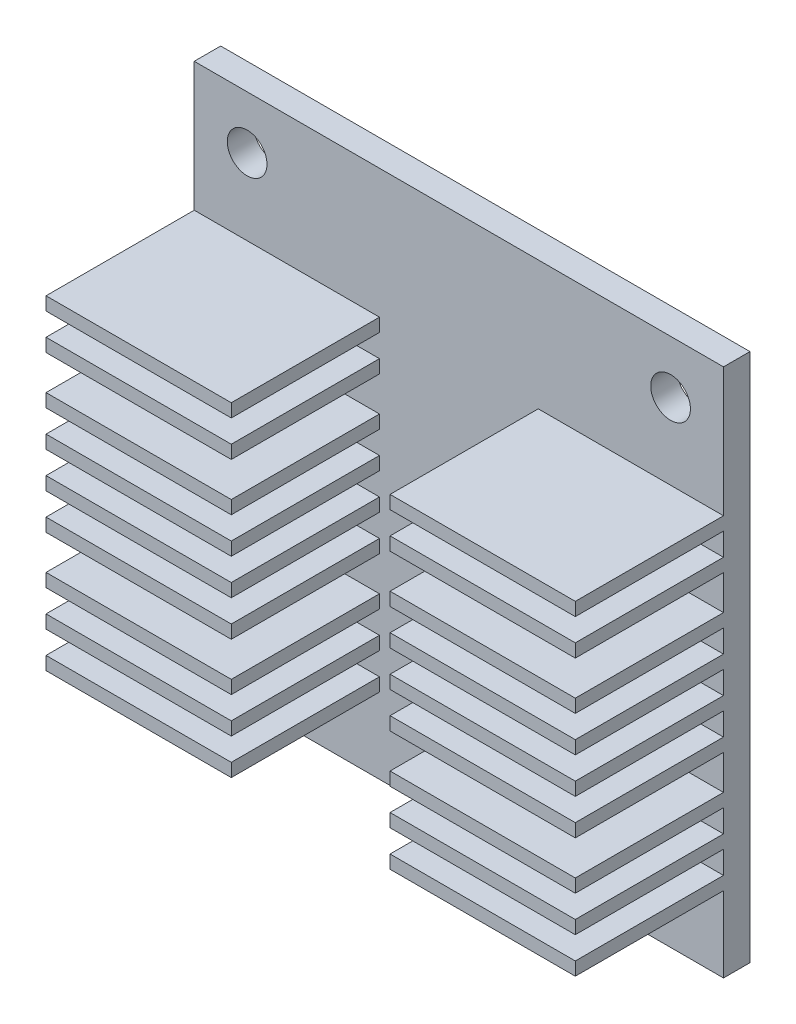
SolidWorks part; units mm, degrees
ref_plane "Front Plane" through (0, 0, 0) normal (0, 0, 1) x (1, 0, 0)
ref_plane "Top Plane" through (0, 0, 0) normal (0, 1, 0) x (1, 0, 0)
ref_plane "Right Plane" through (0, 0, 0) normal (1, 0, 0) x (0, 0, -1)
sketch "Sketch1" plane through (0, 0, 0) normal (0, 0, 1) x (1, 0, 0)
  line L0 (41, 4.4837) -> (27, 4.4837)
  line L1 (41, 2.4837) -> (1, 2.4837)
  line L2 (41, 2.4837) -> (41, 42.4837)
  line L3 (41, 42.4837) -> (1, 42.4837)
  line L4 (1, 2.4837) -> (1, 42.4837)
  line L5 (21, 40.4837) -> (21, 4.4837) construction
  line L6 (41, 21.7785) -> (27, 21.7785) construction
  line L7 (41, 4.4837) -> (41, 40.4837)
  line L8 (27, 4.4837) -> (27, 40.4837)
  line L9 (15, 4.4837) -> (15, 40.4837)
  line L10 (1, 4.4837) -> (1, 40.4837)
  line L11 (25, 4.4837) -> (25, 40.4837)
  line L12 (17, 4.4837) -> (17, 40.4837)
  line L13 (41, 40.4837) -> (27, 40.4837)
  line L14 (41, 5.4837) -> (27, 5.4837)
  line L15 (41, 6.389) -> (27, 6.389)
  line L16 (41, 7.2943) -> (27, 7.2943)
  line L17 (41, 8.1995) -> (27, 8.1995)
  line L18 (41, 9.1048) -> (27, 9.1048)
  line L19 (41, 10.01) -> (27, 10.01)
  line L20 (41, 10.9153) -> (27, 10.9153)
  line L21 (41, 11.8206) -> (27, 11.8206)
  line L22 (41, 12.7258) -> (27, 12.7258)
  line L23 (41, 13.6311) -> (27, 13.6311)
  line L24 (41, 14.5364) -> (27, 14.5364)
  line L25 (41, 15.4416) -> (27, 15.4416)
  line L26 (41, 16.3469) -> (27, 16.3469)
  line L27 (41, 17.2522) -> (27, 17.2522)
  line L28 (41, 18.1574) -> (27, 18.1574)
  line L29 (41, 19.0627) -> (27, 19.0627)
  line L30 (41, 19.9679) -> (27, 19.9679)
  line L31 (41, 20.8732) -> (27, 20.8732)
  line L32 (41, 21.7785) -> (27, 21.7785)
  line L33 (41, 22.6837) -> (27, 22.6837)
  line L34 (41, 23.589) -> (27, 23.589)
  line L35 (41, 24.4943) -> (27, 24.4943)
  line L36 (41, 25.3995) -> (27, 25.3995)
  line L37 (41, 26.3048) -> (27, 26.3048)
  line L38 (41, 27.21) -> (27, 27.21)
  line L39 (41, 28.1153) -> (27, 28.1153)
  line L40 (41, 29.0206) -> (27, 29.0206)
  line L41 (41, 29.9258) -> (27, 29.9258)
  line L42 (41, 30.8311) -> (27, 30.8311)
  line L43 (41, 31.7364) -> (27, 31.7364)
  line L44 (41, 32.6416) -> (27, 32.6416)
  line L45 (41, 33.5469) -> (27, 33.5469)
  line L46 (41, 34.4522) -> (27, 34.4522)
  line L47 (41, 35.3574) -> (27, 35.3574)
  line L48 (41, 36.2627) -> (27, 36.2627)
  line L49 (41, 37.1679) -> (27, 37.1679)
  line L50 (41, 38.0732) -> (27, 38.0732)
  line L51 (46.6374, 3.6837) -> (46.6374, 4.6837) construction
  line L52 (45.6374, 5.4837) -> (-11.288, 5.4837) construction
  line L53 (45.6374, 4.4837) -> (-11.288, 4.4837) construction
  line L54 (25, 4.4837) -> (17, 4.4837)
  line L55 (25, 5.4837) -> (17, 5.4837)
  line L56 (25, 6.389) -> (17, 6.389)
  line L57 (25, 7.2943) -> (17, 7.2943)
  line L58 (25, 8.1995) -> (17, 8.1995)
  line L59 (25, 9.1048) -> (17, 9.1048)
  line L60 (25, 10.01) -> (17, 10.01)
  line L61 (25, 10.9153) -> (17, 10.9153)
  line L62 (25, 11.8206) -> (17, 11.8206)
  line L63 (25, 12.7258) -> (17, 12.7258)
  line L64 (25, 13.6311) -> (17, 13.6311)
  line L65 (25, 14.5364) -> (17, 14.5364)
  line L66 (25, 15.4416) -> (17, 15.4416)
  line L67 (25, 16.3469) -> (17, 16.3469)
  line L68 (25, 17.2522) -> (17, 17.2522)
  line L69 (25, 18.1574) -> (17, 18.1574)
  line L70 (25, 19.0627) -> (17, 19.0627)
  line L71 (25, 19.9679) -> (17, 19.9679)
  line L72 (25, 20.8732) -> (17, 20.8732)
  line L73 (25, 21.7785) -> (17, 21.7785) construction
  line L74 (25, 21.7785) -> (17, 21.7785)
  line L75 (25, 22.6837) -> (17, 22.6837)
  line L76 (25, 23.589) -> (17, 23.589)
  line L77 (25, 24.4943) -> (17, 24.4943)
  line L78 (25, 25.3995) -> (17, 25.3995)
  line L79 (25, 26.3048) -> (17, 26.3048)
  line L80 (25, 27.21) -> (17, 27.21)
  line L81 (25, 28.1153) -> (17, 28.1153)
  line L82 (25, 29.0206) -> (17, 29.0206)
  line L83 (25, 29.9258) -> (17, 29.9258)
  line L84 (25, 30.8311) -> (17, 30.8311)
  line L85 (25, 31.7364) -> (17, 31.7364)
  line L86 (25, 32.6416) -> (17, 32.6416)
  line L87 (25, 33.5469) -> (17, 33.5469)
  line L88 (25, 34.4522) -> (17, 34.4522)
  line L89 (25, 35.3574) -> (17, 35.3574)
  line L90 (25, 36.2627) -> (17, 36.2627)
  line L91 (25, 37.1679) -> (17, 37.1679)
  line L92 (25, 38.0732) -> (17, 38.0732)
  line L93 (25, 40.4837) -> (17, 40.4837)
  line L94 (15, 4.4837) -> (1, 4.4837)
  line L95 (15, 5.4837) -> (1, 5.4837)
  line L96 (15, 6.389) -> (1, 6.389)
  line L97 (15, 7.2943) -> (1, 7.2943)
  line L98 (15, 8.1995) -> (1, 8.1995)
  line L99 (15, 9.1048) -> (1, 9.1048)
  line L100 (15, 10.01) -> (1, 10.01)
  line L101 (15, 10.9153) -> (1, 10.9153)
  line L102 (15, 11.8206) -> (1, 11.8206)
  line L103 (15, 12.7258) -> (1, 12.7258)
  line L104 (15, 13.6311) -> (1, 13.6311)
  line L105 (15, 14.5364) -> (1, 14.5364)
  line L106 (15, 15.4416) -> (1, 15.4416)
  line L107 (15, 16.3469) -> (1, 16.3469)
  line L108 (15, 17.2522) -> (1, 17.2522)
  line L109 (15, 18.1574) -> (1, 18.1574)
  line L110 (15, 19.0627) -> (1, 19.0627)
  line L111 (15, 19.9679) -> (1, 19.9679)
  line L112 (15, 20.8732) -> (1, 20.8732)
  line L113 (15, 21.7785) -> (1, 21.7785) construction
  line L114 (15, 21.7785) -> (1, 21.7785)
  line L115 (15, 22.6837) -> (1, 22.6837)
  line L116 (15, 23.589) -> (1, 23.589)
  line L117 (15, 24.4943) -> (1, 24.4943)
  line L118 (15, 25.3995) -> (1, 25.3995)
  line L119 (15, 26.3048) -> (1, 26.3048)
  line L120 (15, 27.21) -> (1, 27.21)
  line L121 (15, 28.1153) -> (1, 28.1153)
  line L122 (15, 29.0206) -> (1, 29.0206)
  line L123 (15, 29.9258) -> (1, 29.9258)
  line L124 (15, 30.8311) -> (1, 30.8311)
  line L125 (15, 31.7364) -> (1, 31.7364)
  line L126 (15, 32.6416) -> (1, 32.6416)
  line L127 (15, 33.5469) -> (1, 33.5469)
  line L128 (15, 34.4522) -> (1, 34.4522)
  line L129 (15, 35.3574) -> (1, 35.3574)
  line L130 (15, 36.2627) -> (1, 36.2627)
  line L131 (15, 37.1679) -> (1, 37.1679)
  line L132 (15, 38.0732) -> (1, 38.0732)
  line L133 (15, 40.4837) -> (1, 40.4837)
  point P48 (21, 21.7785)
  dimension "D1" = 2
  dimension "D2" = 2
  dimension "D3" = 0
  dimension "D4" = 0
  dimension "D5" = 2
  dimension "D6" = 2
  dimension "D7" = 14
  dimension "D8" = 14
  dimension "D10" = 1
  dimension "D9" = 1
extrude "Boss-Extrude1" add sketch "Sketch1" along normal blind 2 contours L1 L4 L3 L2
extrude "Extrude-Thin1" add sketch "Sketch1<3>" along normal blind 11.2 from surface thin contours L17 | L20 | L98 | L101 | L23 | L104 | L36 | L33 | L30 | L27 | L108 | L111 | L115 | L118 | L40 | L122 | L43 | L125 starting at face at (21, 22.4837, 2) thin type one direction wall 1
sketch "Sketch1<3>" plane through (0, 0, 0) normal (0, 0, 1) x (1, 0, 0) same geometry as "Sketch1"
sketch "Sketch3" plane through (0, 0, 0) normal (0, 0, -1) x (-1, 0, 0)
  line L1 (-21, 2.4837) -> (-21, 42.4837) construction
  line L2 (-5, 38.4837) -> (-37, 38.4837) construction
  line L3 (-5, 38.4837) -> (-5, 6.4837) construction
  line L4 (-5, 6.4837) -> (-37, 6.4837) construction
  line L5 (-37, 38.4837) -> (-37, 6.4837) construction
  line L6 (-21, 6.4837) -> (-21, 38.4837) construction
  line L7 (-5, 22.4837) -> (-37, 22.4837) construction
  line L8 (-41, 2.4837) -> (-1, 2.4837) construction
  line L9 (-41, 42.4837) -> (-1, 42.4837) construction
  line L10 (-41, 22.4837) -> (-1, 22.4837) construction
  line L11 (-41, 2.4837) -> (-41, 42.4837) construction
  line L12 (-1, 2.4837) -> (-1, 42.4837) construction
  circle A0 centre (-37, 6.4837) radius 1.5
  circle A1 centre (-5, 6.4837) radius 1.5
  circle A2 centre (-5, 38.4837) radius 1.5
  circle A3 centre (-37, 38.4837) radius 1.5
  point P141 (-21, 22.4837)
  dimension "D1" = 3
  dimension "D4" = 3
  dimension "D5" = 3
  dimension "D6" = 3
  dimension "D2" = 32
  dimension "D3" = 32
extrude "Cut-Extrude1" cut sketch "Sketch3" against normal up to surface (13.2 mm away) from surface contours A0 up to face at (34, 8.6995, 13.2) starting at face at (21, 22.4837, 0)
pattern_linear "LPattern1" count 2 spacing 32 along (-1, 0, 0) count 2 spacing 32 along (0, 1, 0) of "Cut-Extrude1"
